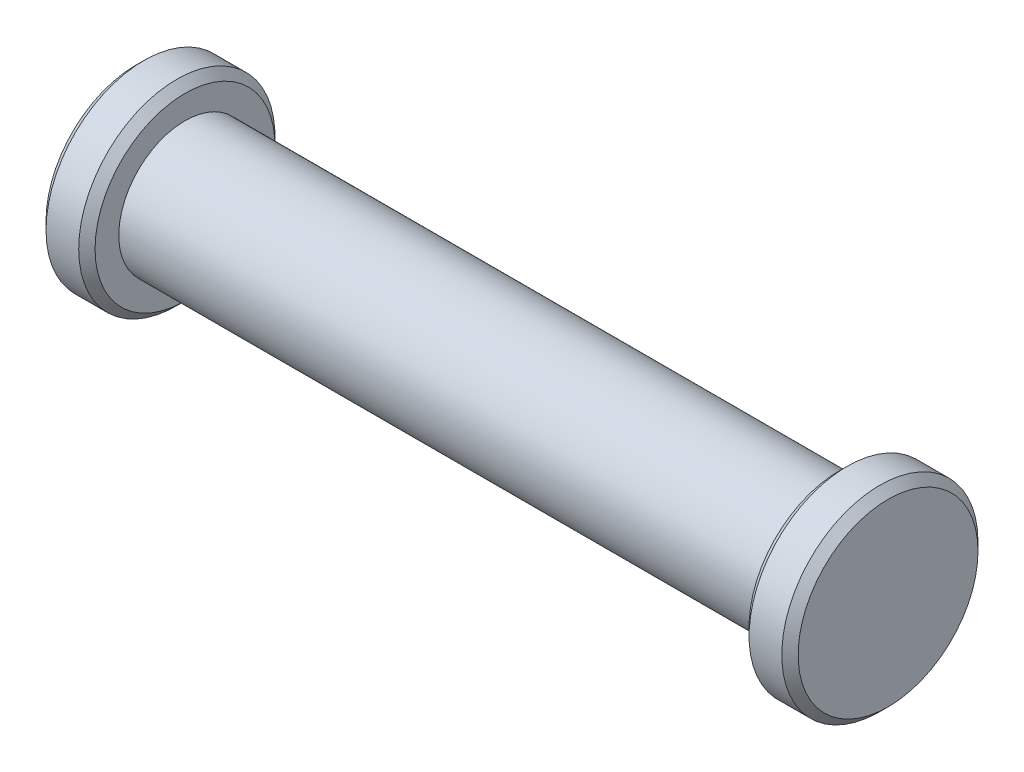
SolidWorks part; units mm, degrees
ref_plane "Front Plane" through (0, 0, 0) normal (0, 0, 1) x (1, 0, 0)
ref_plane "Top Plane" through (0, 0, 0) normal (0, 1, 0) x (1, 0, 0)
ref_plane "Right Plane" through (0, 0, 0) normal (1, 0, 0) x (0, 0, -1)
sketch "Sketch1" plane through (0, 0, 0) normal (1, 0, 0) x (0, 0, -1)
  circle A0 centre (0, 0) radius 4.05
  dimension "D1" = 8.1
extrude "Boss-Extrude1" add sketch "Sketch1" along normal blind 40
sketch "Sketch2" plane through (40, 0, 0) normal (1, 0, 0) x (0, 0, -1)
  circle A0 centre (0, 0) radius 6
  dimension "D1" = 12
extrude "Boss-Extrude2" add sketch "Sketch2" along normal blind 3
sketch "Sketch3" plane through (0, 0, 0) normal (0, 0, 1) x (1, 0, 0)
  line L0 (6.6, 0) -> (-6.6, 0) construction
  line L1 (0, -6.6) -> (0, 6.6) construction
  circle A0 centre (4, 0) radius 1.5
  dimension "D1" = 3
  dimension "D2" = 4
extrude "Cut-Extrude1" [suppressed] cut sketch "Sketch3" against normal through all both and the other way through all
chamfer "Chamfer1" [suppressed] distance 0.5 angle 45
sketch "Sketch4" plane through (0, 0, 0) normal (-1, 0, 0) x (0, 0, 1)
  circle A0 centre (0, 0) radius 6
extrude "Boss-Extrude3" add sketch "Sketch4" along normal blind 3
chamfer "Chamfer2" distance 0.5 angle 45 4 edges at (43, 0, -6) (40, 0, -6) (0, 0, 6) (-3, 0, 6)
